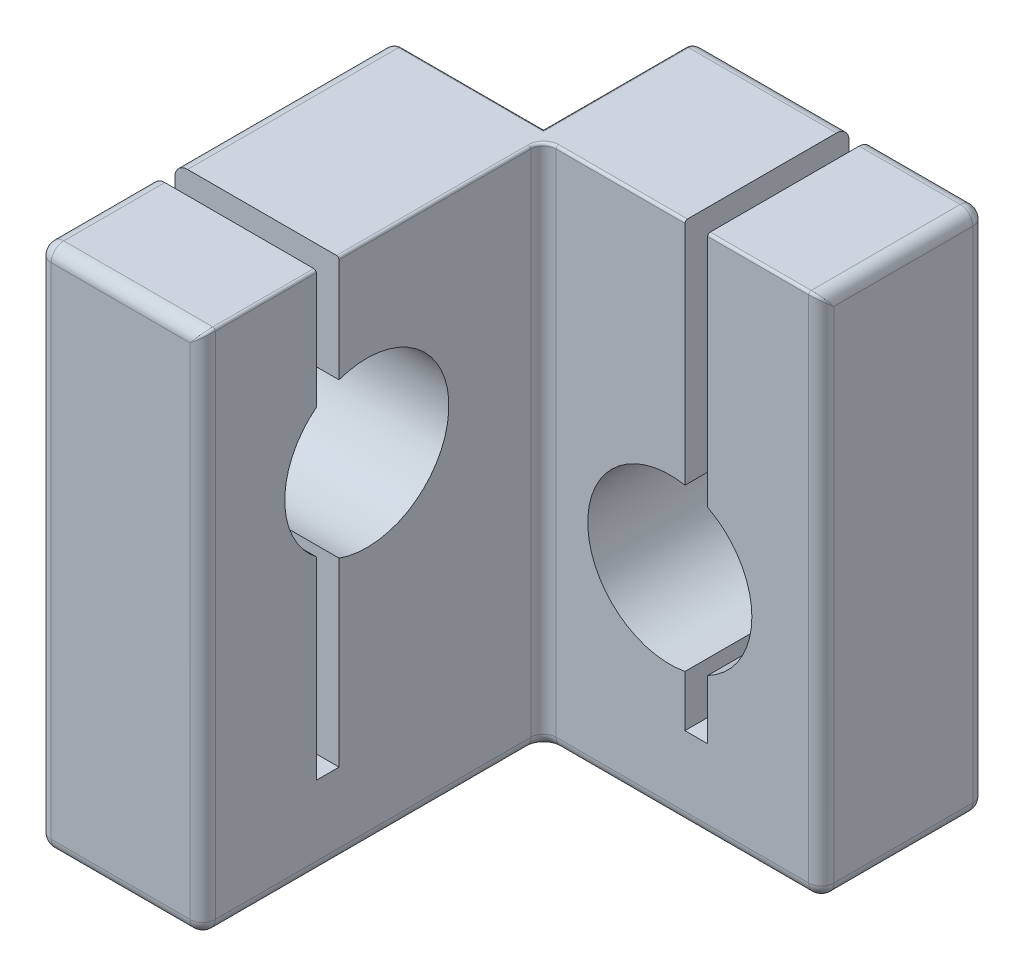
SolidWorks part; units mm, degrees
other "Markup1"
sketch "Sketch8"
ref_plane "Front Plane" through (0, 0, 0) normal (0, 0, 1) x (1, 0, 0)
ref_plane "Top Plane" through (0, 0, 0) normal (0, 1, 0) x (1, 0, 0)
ref_plane "Right Plane" through (0, 0, 0) normal (1, 0, 0) x (0, 0, -1)
sketch "Sketch1" plane through (0, 0, 0) normal (0, 1, 0) x (1, 0, 0)
  line L0 (0, 0) -> (0, -40)
  line L1 (0, -40) -> (13, -40)
  line L2 (13, -40) -> (13, -13)
  line L3 (13, -13) -> (35, -13)
  line L4 (35, -13) -> (35, 0)
  line L5 (35, 0) -> (0, 0)
  dimension "D1" = 13
  dimension "D2" = 13
  dimension "D3" = 40
  dimension "D4" = 35
extrude "Boss-Extrude1" add sketch "Sketch1" along normal blind 41.55
sketch "Sketch2" plane through (0, 41.55, 0) normal (0, 1, 0) x (1, 0, 0)
  line L0 (0, 0) -> (13, -13) construction
  line L5 (0, 0) -> (12.2929, 0)
  line L6 (0, 0) -> (0, -12.2929)
  line L7 (0, -12.2929) -> (12.2929, -12.2929)
  line L8 (12.2929, 0) -> (12.2929, -12.2929)
  line L9 (13, -40) -> (13, -13) construction
  line L10 (13, -13) -> (35, -13) construction
  point P6 (10.5458, -10.5458)
  point P13 (11.8187, -11.8187)
  dimension "D1" = 1
extrude "Cut-Extrude1" cut sketch "Sketch2" against normal blind 13.25
fillet "Fillet1" radius 4 1 edges at (12.2929, 28.3, 6.1464)
fillet "Fillet2" radius 1 21 edges at (23.6464, 41.55, 0) (12.2929, 36.925, 0) (11.1213, 29.4716, 0) (4.1464, 28.3, 0) (0, 14.15, 0) (0, 28.3, 6.1464) (0, 34.925, 12.2929) (0, 41.55, 26.1464) (0, 0, 20) (17.5, 0, 0) (35, 41.55, 6.5) (35, 20.775, 0) (35, 0, 6.5) (13, 0, 26.5) (13, 20.775, 13) (35, 20.775, 13) (24, 0, 13) (0, 20.775, 40) (6.5, 41.55, 40) (13, 20.775, 40) (6.5, 0, 40)
fillet "Fillet3" radius 0.2 9 edges at (0.2929, 41.2571, 12.5858) (12.5858, 41.2571, 0.2929) (6.6464, 41.55, 12.2929) (12.2929, 41.55, 6.6464) (12.7071, 41.2571, 39.7071) (34.7071, 41.2571, 12.7071) (24, 41.55, 13) (13.2929, 41.55, 13.2929) (13, 41.55, 26.5)
sketch "Sketch3" plane through (0, 41.55, 0) normal (0, 1, 0) x (1, 0, 0)
  line L0 (12, -40) -> (1, -40) construction
  line L1 (0, -31) -> (13, -31)
  line L2 (0, -31) -> (0, -29.2)
  line L3 (0, -29.2) -> (13, -29.2)
  line L4 (13, -31) -> (13, -29.2)
  line L5 (0, -31) -> (13, -29.2) construction
  line L6 (0, -29.2) -> (13, -31) construction
  line L7 (24.2, -13) -> (26, -13)
  line L8 (24.2, -13) -> (24.2, 0)
  line L9 (24.2, 0) -> (26, 0)
  line L10 (26, -13) -> (26, 0)
  line L11 (24.2, -13) -> (26, 0) construction
  line L12 (24.2, 0) -> (26, -13) construction
  line L13 (35, -1) -> (35, -12) construction
  line L14 (13, -14) -> (13, -39) construction
  line L15 (0, -39) -> (0, -13.2929) construction
  line L16 (34, -13) -> (14, -13) construction
  line L17 (13.2929, 0) -> (34, 0) construction
  point P0 (6.5, -30.1)
  point P5 (25.1, -6.5)
  dimension "D1" = 9
  dimension "D2" = 9
  dimension "D3" = 1.8
  dimension "D4" = 1.8
extrude "Cut-Extrude2" cut sketch "Sketch3" against normal blind 35
sketch "Sketch4" plane through (0, 0, 13) normal (0, 0, 1) x (1, 0, 0)
  line L0 (34, 0) -> (14, 0) construction
  line L2 (35, 40.55) -> (35, 1) construction
  circle A0 centre (23, 17) radius 6.5
  point P5 (0, 0)
  point P8 (0, 0)
  dimension "D2" = 13
  dimension "D1" = 17
  dimension "D3" = 12
extrude "Cut-Extrude3" cut sketch "Sketch4" against normal blind 35
sketch "Sketch5" plane through (13, 0, 0) normal (1, 0, 0) x (0, 0, -1)
  line L0 (-14, 0) -> (-39, 0) construction
  line L2 (-40, 1) -> (-40, 40.55) construction
  circle A0 centre (-27, 27) radius 6.5
  point P5 (0, 0)
  point P8 (0, 0)
  dimension "D1" = 13
  dimension "D2" = 27
  dimension "D3" = 13
extrude "Cut-Extrude4" cut sketch "Sketch5" against normal blind 35
sketch "Sketch6" plane through (0, 0, 0) normal (0, -1, 0) x (1, 0, 0)
  line L0 (14, 13) -> (34, 13) construction
  line L1 (35, 12) -> (35, 1) construction
  line L2 (0, 1) -> (0, 39) construction
  line L3 (1, 40) -> (12, 40) construction
  circle A0 centre (5, 27.5) radius 2
  circle A1 centre (5, 15) radius 2
  circle A2 centre (29, 6) radius 2
  point P6 (0, 0)
  dimension "D1" = 4
  dimension "D2" = 7
  dimension "D3" = 6
  dimension "D4" = 5
  dimension "D5" = 12.5
  dimension "D6" = 25
extrude "Cut-Extrude5" cut sketch "Sketch6" against normal blind 10.3
